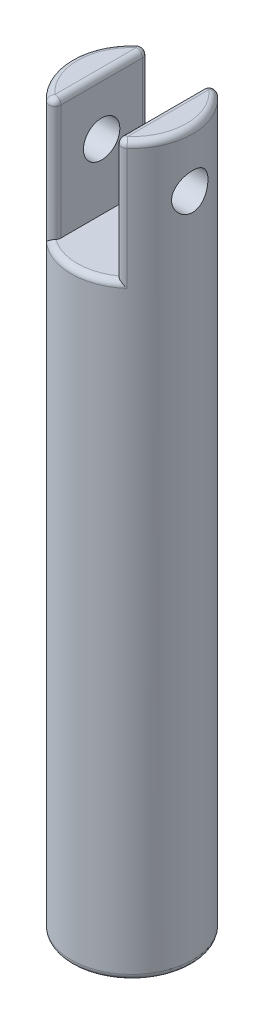
SolidWorks part; units mm, degrees
material "Plain Carbon Steel"
ref_plane "Front Plane" through (0, 0, 0) normal (0, 0, 1) x (1, 0, 0)
ref_plane "Top Plane" through (0, 0, 0) normal (0, 1, 0) x (1, 0, 0)
ref_plane "Right Plane" through (0, 0, 0) normal (1, 0, 0) x (0, 0, -1)
sketch "Sketch1" plane through (0, 0, 0) normal (0, 1, 0) x (1, 0, 0)
  circle A0 centre (0, 0) radius 100
extrude "Boss-Extrude1" add sketch "Sketch1" along normal blind 1200 contours A0
sketch "Sketch2" plane through (0, 1200, 0) normal (0, 1, 0) x (1, 0, 0)
  line L2 (50, -86.6025) -> (50, 86.6025)
  line L4 (-50, -86.6025) -> (-50, 86.6025)
  circle A0 centre (0, 0) radius 100 construction
  arc A1 (-50, 86.6025) -> (50, 86.6025) centre (0, 0) cw
  arc A2 (-50, -86.6025) -> (50, -86.6025) centre (0, 0) ccw
  point P0 (0, 0)
extrude "Cut-Extrude1" cut sketch "Sketch2" against normal blind 200 contours A2 L2 A1 L4
sketch "Sketch3" plane through (50, 0, 0) normal (-1, 0, 0) x (0, 0, 1)
  circle A0 centre (0, 1107.9431) radius 30
extrude "Cut-Extrude3" cut sketch "Sketch3" against normal through all both and the other way through all
fillet "Fillet1" radius 10 1 edges at (-50, 1100, 86.6025)
fillet "Fillet2" radius 10 1 edges at (-10.2882, 1000, 99.4694)
fillet "Fillet3" radius 10 1 edges at (50, 1095, 86.6025)
fillet "Fillet4" radius 10 3 edges at (-50, 1100, -86.6025) (50, 1100, -86.6025) (0, 1000, -100)
fillet "Fillet5" radius 10 9 edges at (-55.9175, 1200, 76.2107) (-100, 1200, 0) (-55.9175, 1200, -76.2107) (55.9175, 1200, 76.2107) (100, 1200, 0) (55.9175, 1200, -76.2107) (0, 0, 100) (-50, 1200, 0) (50, 1200, 0)
